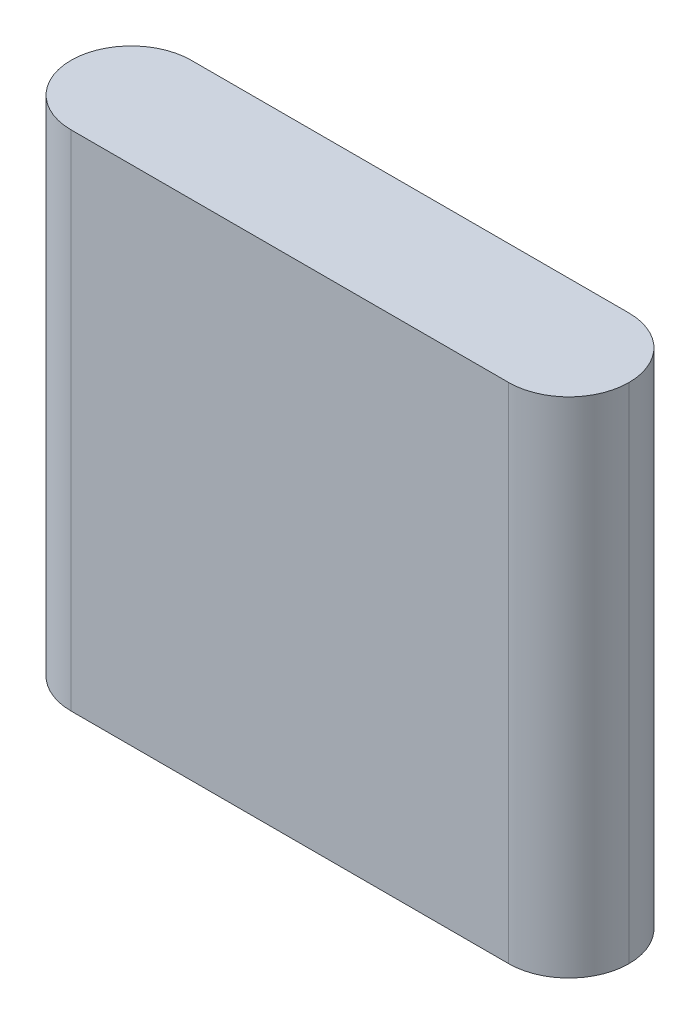
SolidWorks part; units mm, degrees
ref_plane "Front" through (0, 0, 0) normal (0, 0, 1) x (1, 0, 0)
ref_plane "Top" through (0, 0, 0) normal (0, 1, 0) x (1, 0, 0)
ref_plane "Right" through (0, 0, 0) normal (1, 0, 0) x (0, 0, -1)
sketch "Sketch1" plane through (0, 0, 0) normal (0, 0, 1) x (1, 0, 0)
  line L1 (-25.5, 23) -> (25.5, 23)
  line L2 (-25.5, 23) -> (-25.5, -23)
  line L3 (-25.5, -23) -> (25.5, -23)
  line L4 (25.5, 23) -> (25.5, -23)
  line L5 (-25.5, 23) -> (25.5, -23) construction
  line L6 (-25.5, -23) -> (25.5, 23) construction
  point P0 (0, 0)
  dimension "D1" = 51
  dimension "D2" = 46
extrude "Boss-Extrude1" add sketch "Sketch1" along normal blind 11
fillet "Fillet2" radius 5.5 1 edges at (25.5, 0, 11)
fillet "Fillet3" radius 5.5 3 edges at (-25.5, 0, 11) (-25.5, 0, 0) (25.5, 0, 0)
